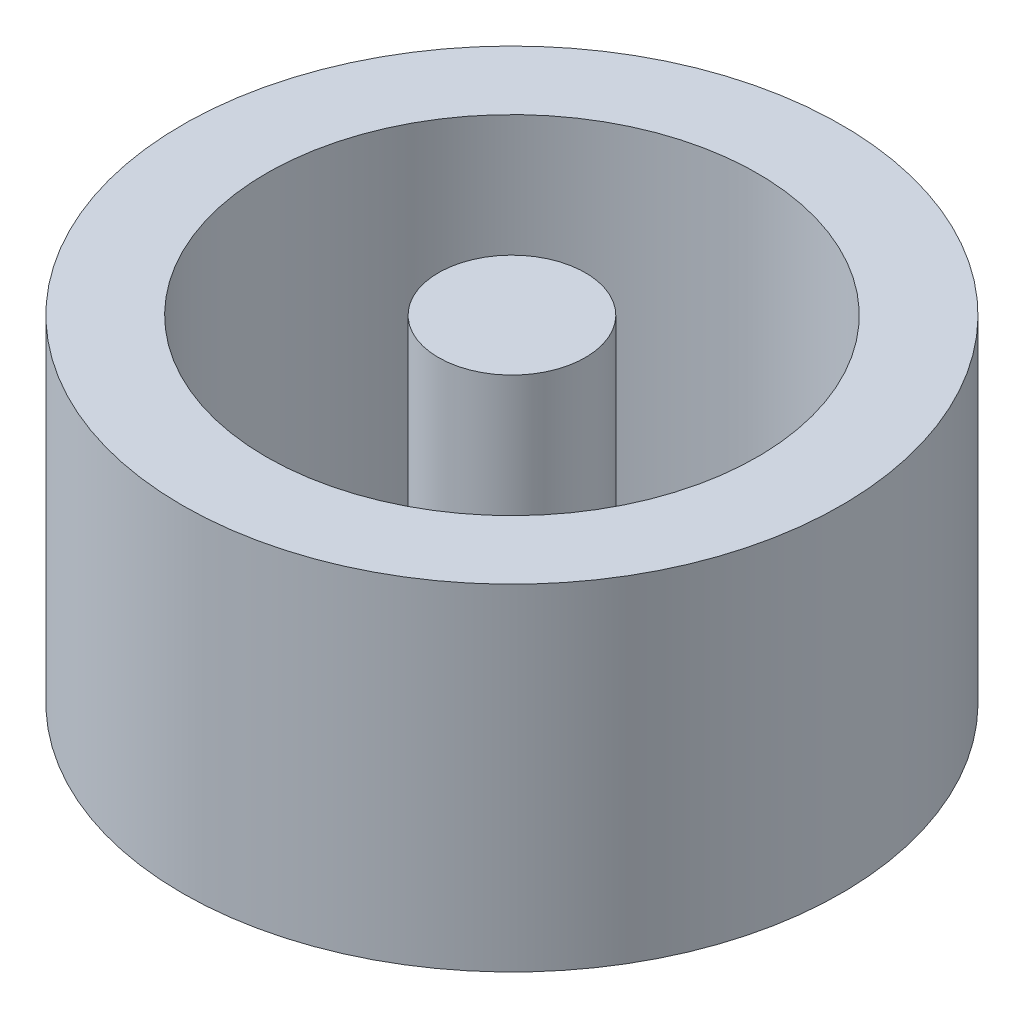
SolidWorks part; units mm, degrees
ref_plane "Front Plane" through (0, 0, 0) normal (0, 0, 1) x (1, 0, 0)
ref_plane "Top Plane" through (0, 0, 0) normal (0, 1, 0) x (1, 0, 0)
ref_plane "Right Plane" through (0, 0, 0) normal (1, 0, 0) x (0, 0, -1)
sketch "Sketch1" plane through (0, 0, 0) normal (0, 1, 0) x (1, 0, 0)
  circle A0 centre (0, 0) radius 0.875
  circle A1 centre (0, 0) radius 2.925
  circle A2 centre (0, 0) radius 3.925
  dimension "D1" = 5.85
  dimension "D2" = 1.75
  dimension "D3" = 1
extrude "Boss-Extrude1" add sketch "Sketch1" along normal blind 4 contours A2 A1 | A0 region at (0, 0, 0) region at (-3.814, 0, 0)
equation "\"D1@Sketch1\"=5.75mm+0.1mm"
equation "\"D2@Sketch1\"=1.85 - 0.1"
